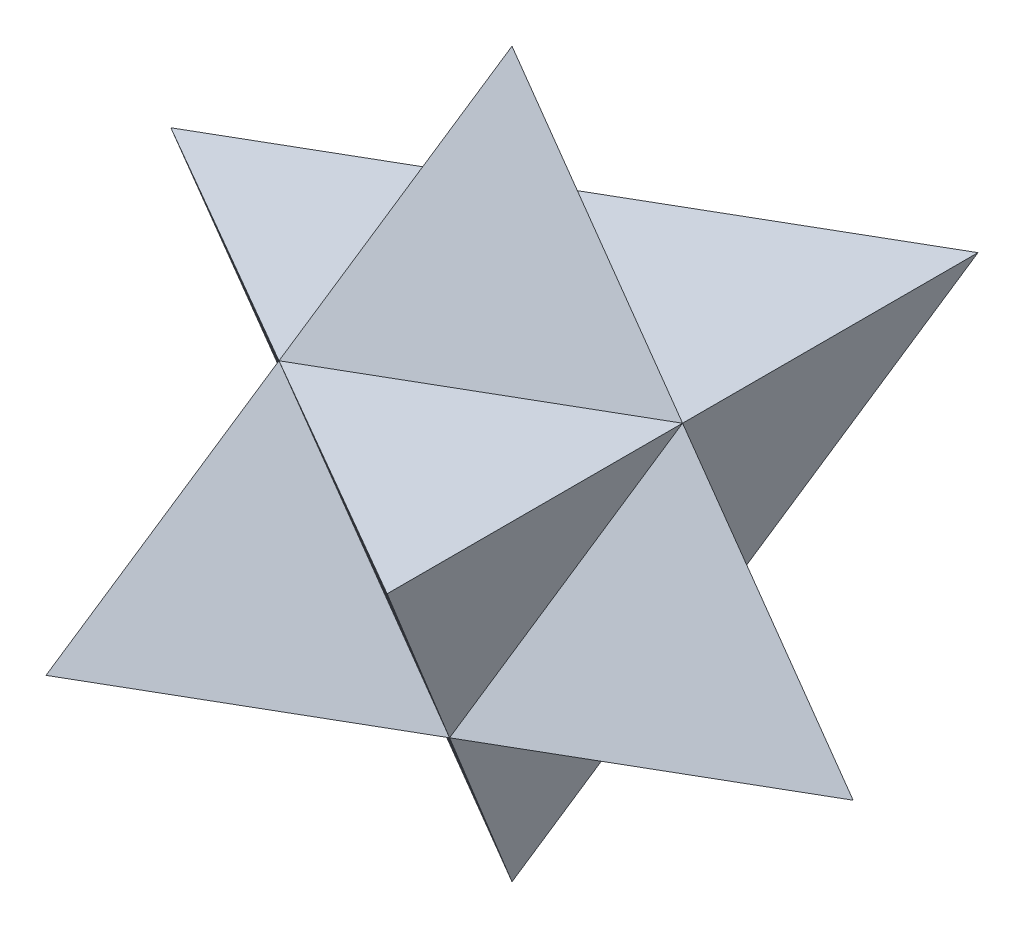
SolidWorks part; units mm, degrees
note: '?' marks a value the reader was unsure of.
ref_plane "Front Plane" through (0, 0, 0) normal (0, 0, 1) x (1, 0, 0)
ref_plane "Top Plane" through (0, 0, 0) normal (0, 1, 0) x (1, 0, 0)
ref_plane "Right Plane" through (0, 0, 0) normal (1, 0, 0) x (0, 0, -1)
sketch "Sketch8" plane through (0, 0, 0) normal (0, 0, 1) x (1, 0, 0)
  line L0 (0, 0) -> (0, -10) construction
  circle A0 centre (0, 0) radius 10 construction
  point P3 (0, -10)
  dimension "D1" = 10
sketch "Sketch10" plane through (0, 0, 0) normal (0, 0, 1) x (1, 0, 0)
  line L0 (0, -10) -> (-14.1421, -10) construction
  line L1 (-14.1421, -10) -> (-9.4281, 3.3333) construction
  line L2 (-9.4281, 3.3333) -> (-4.714, 16.6667) construction
  line L3 (-4.714, 16.6667) -> (0, 30) construction
  line L4 (0, -10) -> (14.1421, -10) construction
  line L5 (14.1421, -10) -> (28.2843, -10) construction
  line L6 (0, 30) -> (28.2843, -10) construction
  circle A1 centre (0, 0) radius 10 construction
  point P5 (0, 0)
  point P6 (18.9392, -10)
  point P12 (27.9031, -10)
  point P13 (0, 0)
  point P14 (0, -10)
ref_plane "Plane2" through (0, -10, 0) normal (0, 1, 0) x (1, 0, 0)
sketch "Sketch11" plane through (0, -10, 0) normal (0, 1, 0) x (1, 0, 0)
  line L1 (28.2843, 0) -> (-14.1421, 24.4949)
  line L2 (-14.1421, 24.4949) -> (-14.1421, -24.4949)
  line L3 (-14.1421, -24.4949) -> (28.2843, 0)
  circle A0 centre (0, 0) radius 14.1421 construction
  point P1 (26.0764, 0)
  point P7 (-2.9886, 0)
  point P9 (19.3185, 0)
extrude "Boss-Extrude2" add sketch "Sketch11" along normal up to vertex (40 mm away) draft 19.471
ref_axis "Axis2" through (0, 0, 0) along (0, 0, 1)?
pattern_circular "CirPattern2" count 2 over 360 about axis through (0, 0, 0) along (0, 0, 1) of bodies 103
combine bodies "Combine1" bodies to combine 103 104
equation "\"angle\"= arcsin ( 1 / 3 )"
equation "\"D3@Boss-Extrude2\"=\"angle\""
